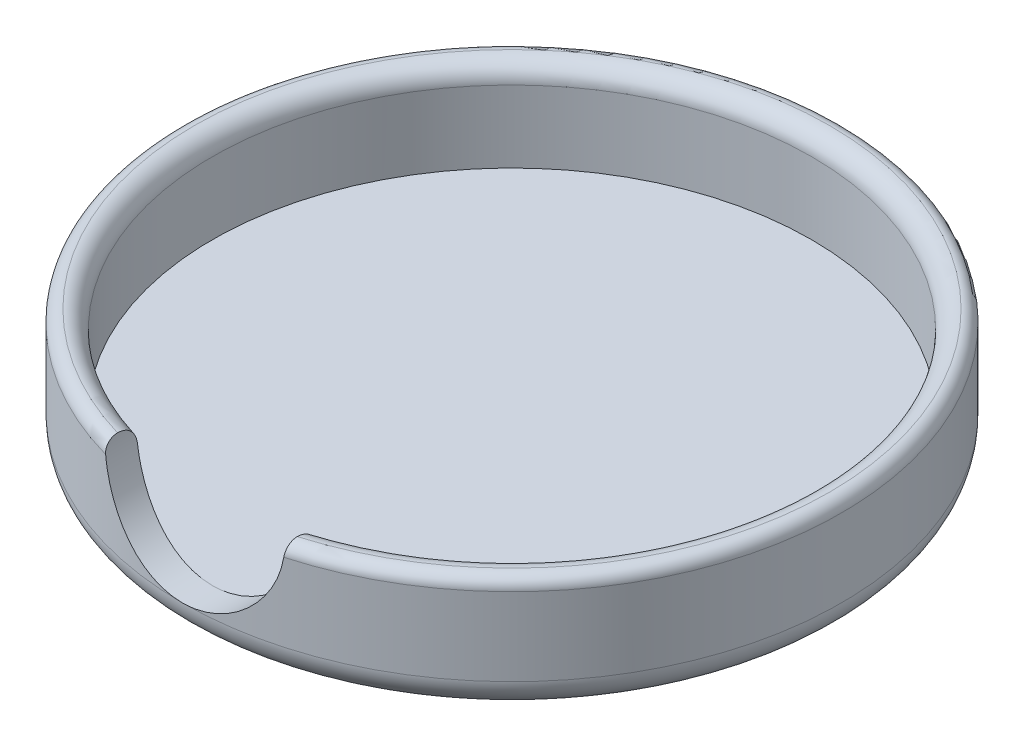
SolidWorks part; units mm, degrees
ref_plane "Front Plane" through (0, 0, 0) normal (0, 0, 1) x (1, 0, 0)
ref_plane "Top Plane" through (0, 0, 0) normal (0, 1, 0) x (1, 0, 0)
ref_plane "Right Plane" through (0, 0, 0) normal (1, 0, 0) x (0, 0, -1)
sketch "Sketch1" plane through (0, 0, 0) normal (0, 1, 0) x (1, 0, 0)
  circle A0 centre (0, 0) radius 55
  dimension "D1" = 110
extrude "Boss-Extrude1" add sketch "Sketch1" along normal blind 5
fillet "Fillet1" radius 5 1 edges at (0, 0, 55)
ref_plane "Plane1" through (0, 5, 0) normal (0, 1, 0) x (1, 0, 0)
sketch "Sketch2" plane through (0, 5, 0) normal (0, 1, 0) x (1, 0, 0)
  circle A0 centre (0, 0) radius 55
  circle A1 centre (0, 0) radius 50
  dimension "D2" = 5
  dimension "D1" = 5
extrude "Boss-Extrude2" add sketch "Sketch2" along normal blind 15
ref_plane "Plane2" through (0, 0, 55) normal (0, 0, 1) x (1, 0, 0)
sketch "Sketch3" plane through (0, 0, 55) normal (0, 0, 1) x (1, 0, 0)
  line L1 (55, 20) -> (-55, 20) construction
  circle A1 centre (0, 20) radius 15
  dimension "D1" = 30
extrude "Cut-Extrude1" cut sketch "Sketch3" against normal blind 30
fillet "Fillet2" radius 3 1 edges at (0, 20, -50)
fillet "Fillet3" radius 2 1 edges at (0, 20, -55)
